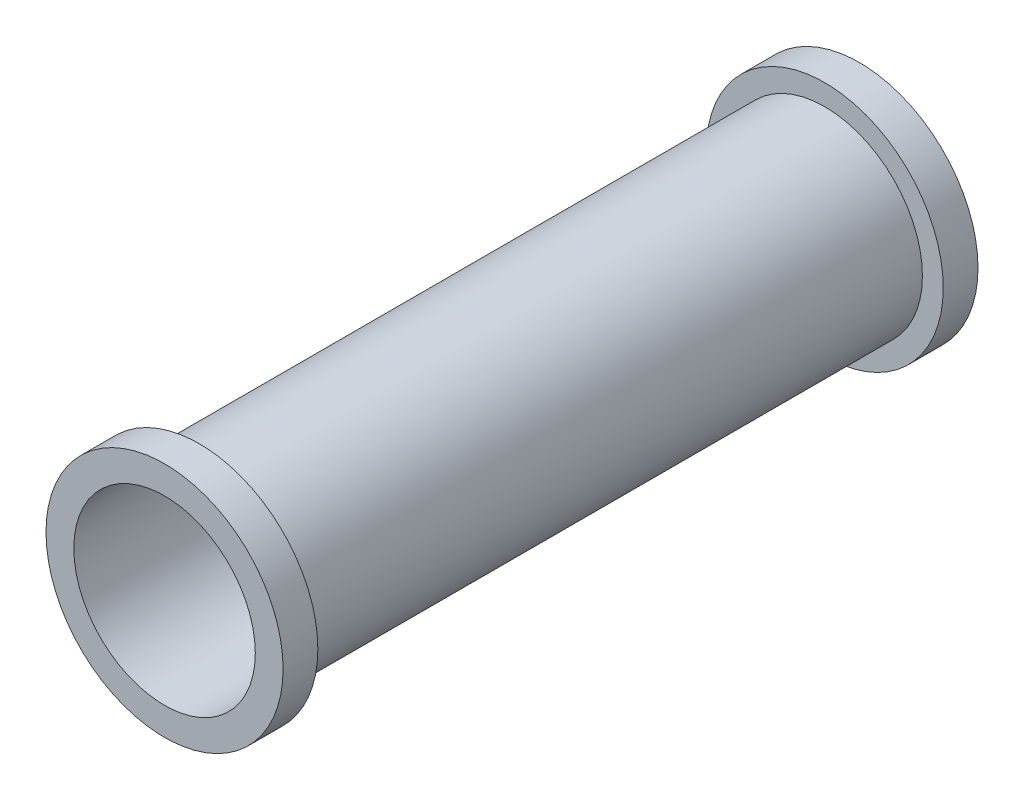
SolidWorks part; units mm, degrees
ref_plane "Plan de face" through (0, 0, 0) normal (0, 0, 1) x (1, 0, 0)
ref_plane "Plan de dessus" through (0, 0, 0) normal (0, 1, 0) x (1, 0, 0)
ref_plane "Plan de droite" through (0, 0, 0) normal (1, 0, 0) x (0, 0, -1)
sketch "Esquisse1" plane through (0, 0, 0) normal (0, 0, 1) x (1, 0, 0)
  circle A0 centre (0, 0) radius 13.0591
  circle A1 centre (0, 0) radius 14.0591
  circle A2 centre (0, 0) radius 17.0591
  dimension "D1" = 1
  dimension "D2" = 3
extrude "Boss.-Extru.3" add sketch "Esquisse1" along normal blind 100 contours A0 | A1
extrude "Boss.-Extru.4" add sketch "Esquisse1<6>" along normal blind 5 contours A2 A1 region at (-16.5766, 0, 0)
sketch "Esquisse1<6>" plane through (0, 0, 0) normal (0, 0, 1) x (1, 0, 0) same geometry as "Esquisse1"
sketch "Esquisse2" plane through (0, 0, 100) normal (0, 0, 1) x (1, 0, 0)
  circle A0 centre (0, 0) radius 14.0591
  circle A1 centre (0, 0) radius 17.0591
  dimension "D1" = 3
extrude "Boss.-Extru.5" add sketch "Esquisse2" against normal blind 5
